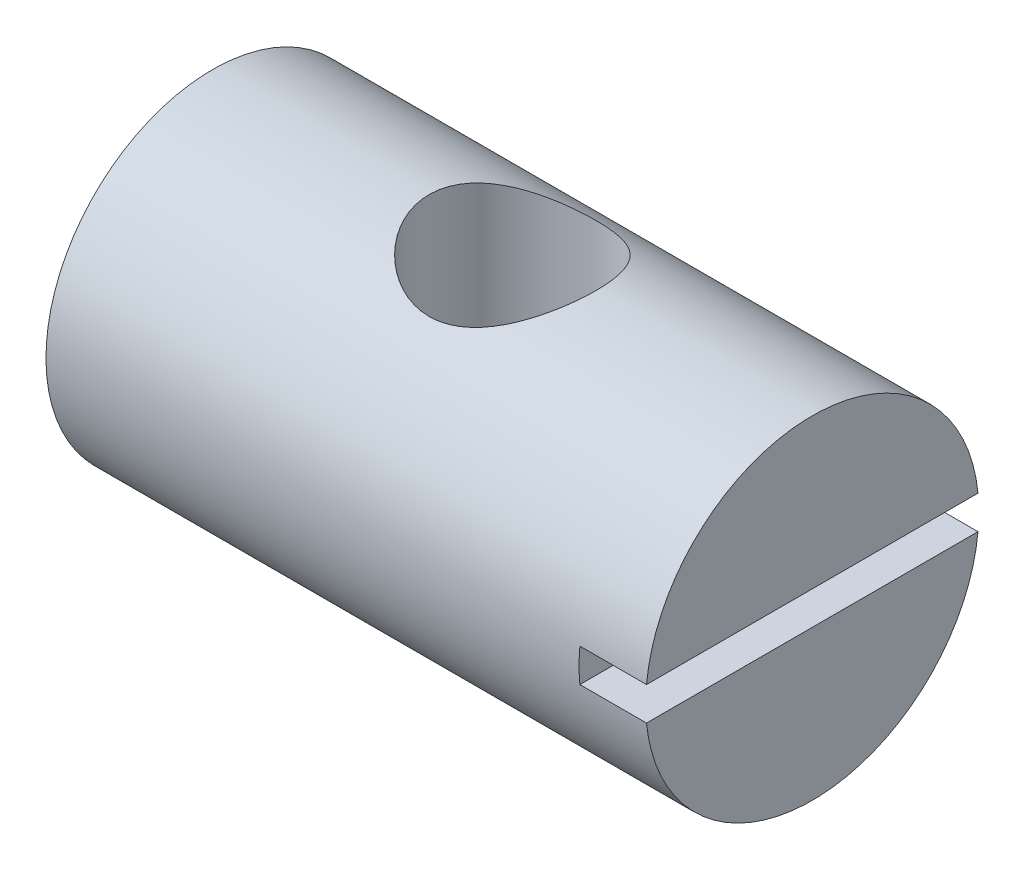
SolidWorks part; units mm, degrees
ref_plane "Front" through (0, 0, 0) normal (0, 0, 1) x (1, 0, 0)
ref_plane "Top" through (0, 0, 0) normal (0, 1, 0) x (1, 0, 0)
ref_plane "Right" through (0, 0, 0) normal (1, 0, 0) x (0, 0, -1)
sketch "Sketch1" plane through (0, 0, 0) normal (1, 0, 0) x (0, 0, -1)
  circle A0 centre (0, 0) radius 5
  dimension "D1" = 10
extrude "Boss-Extrude1" add sketch "Sketch1" against normal blind 9 and the other way blind 9 contours A0
sketch "Sketch7" plane through (0, 0, 0) normal (0, 1, 0) x (1, 0, 0)
  circle A0 centre (0, 0) radius 2.5
  dimension "D1" = 5
extrude "Cut-Extrude1" cut sketch "Sketch7" against normal through all both and the other way through all
sketch "Sketch8" plane through (9, 0, 0) normal (1, 0, 0) x (0, 0, -1)
  line L1 (-5.4328, 0.5) -> (5.4328, 0.5)
  line L2 (-5.4328, 0.5) -> (-5.4328, -0.5)
  line L3 (-5.4328, -0.5) -> (5.4328, -0.5)
  line L4 (5.4328, 0.5) -> (5.4328, -0.5)
  line L5 (-5.4328, 0.5) -> (5.4328, -0.5) construction
  line L6 (-5.4328, -0.5) -> (5.4328, 0.5) construction
  point P0 (0, 0)
  dimension "D1" = 1
extrude "Cut-Extrude2" cut sketch "Sketch8" against normal blind 2
